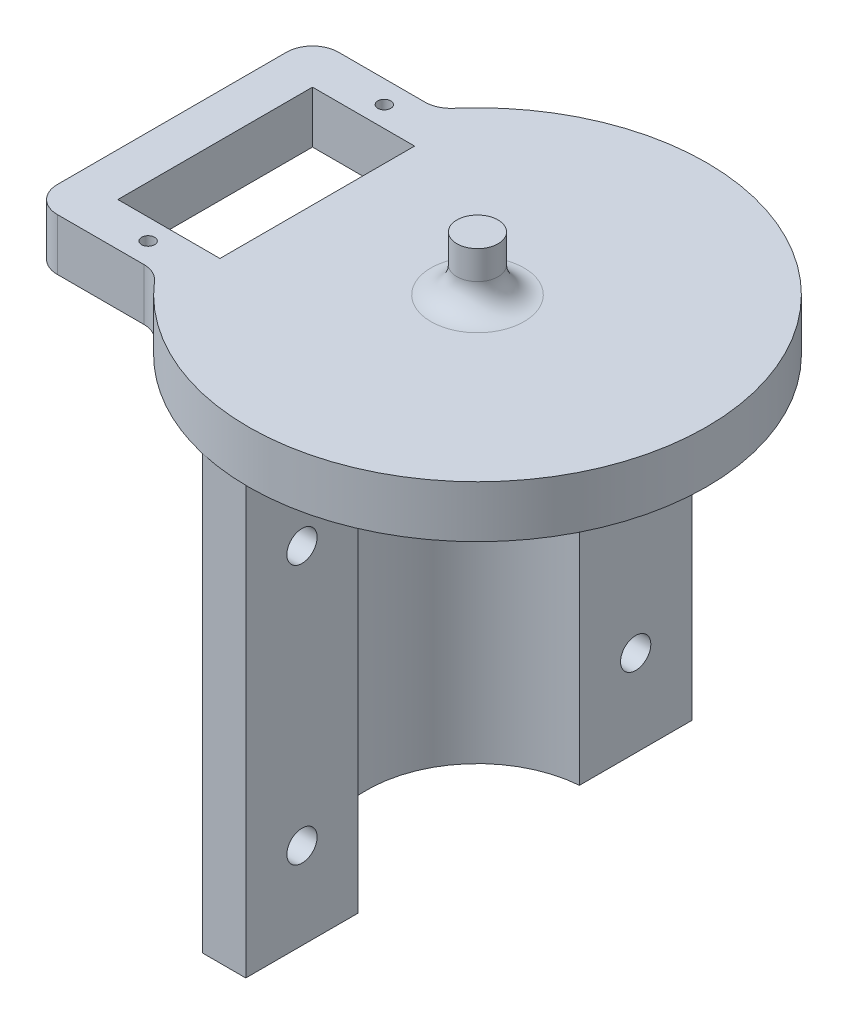
SolidWorks part; units mm, degrees
ref_plane "Front Plane" through (0, 0, 0) normal (0, 0, 1) x (1, 0, 0)
ref_plane "Top Plane" through (0, 0, 0) normal (0, 1, 0) x (1, 0, 0)
ref_plane "Right Plane" through (0, 0, 0) normal (1, 0, 0) x (0, 0, -1)
sketch "Sketch6" plane through (0, 0, 0) normal (0, -1, 0) x (1, 0, 0)
  line L5 (-1, 25.7848) -> (-1, 12.786)
  line L6 (-1, 25.7848) -> (-6, 25.7848)
  line L7 (-6, 25.7848) -> (-6, 16.7848)
  line L8 (-6, -16.7848) -> (-6, -25.7848)
  line L9 (-6, -25.7848) -> (-1, -25.7848)
  line L10 (-1, -25.7848) -> (-1, -12.786)
  line L11 (-12.825, 0) -> (-17.825, 0) construction
  arc A0 (-1, 12.786) -> (-1, -12.786) centre (0, 0) ccw
  arc A1 (-6, 16.7848) -> (-6, -16.7848) centre (0, 0) ccw
  dimension "D1" = 25.65
  dimension "D2" = 5
  dimension "D3" = 1
  dimension "D4" = 9
extrude "Boss-Extrude4" add sketch "Sketch6" along normal blind 50
sketch "Sketch7" plane through (-1, 0, 0) normal (1, 0, 0) x (0, 0, -1)
  line L0 (-19.2854, -50) -> (-19.2854, 0) construction
  line L3 (0, 0) -> (0, -50) construction
  line L6 (-25.7848, -25) -> (25.7848, -25) construction
  line L11 (-12.786, 0) -> (-25.7848, 0) construction
  line L12 (-12.786, -50) -> (-25.7848, -50) construction
  line L13 (-25.7848, -50) -> (-25.7848, 0) construction
  line L14 (25.7848, -50) -> (25.7848, 0) construction
  line L15 (-12.786, -50) -> (12.786, -50) construction
  circle A0 centre (-19.2854, -10) radius 1.75
  circle A1 centre (-19.2854, -40) radius 1.75
  circle A2 centre (19.2854, -40) radius 1.75
  circle A3 centre (19.2854, -10) radius 1.75
  dimension "D1" = 10
  dimension "D2" = 3.5
extrude "Cut-Extrude1" cut sketch "Sketch7" against normal through all
sketch "Sketch8" plane through (0, 0, 0) normal (0, 1, 0) x (1, 0, 0)
  line L0 (-24.4208, -13.65) -> (-24.4208, 13.65) construction
  line L1 (-30.3208, -11.25) -> (-18.5208, -11.25)
  line L2 (-30.3208, -11.25) -> (-30.3208, 11.25)
  line L3 (-30.3208, 11.25) -> (-18.5208, 11.25)
  line L4 (-18.5208, -11.25) -> (-18.5208, 11.25)
  line L5 (-32.3208, -16.25) -> (-22.319, -16.25)
  line L6 (-35.3208, -13.25) -> (-35.3208, 13.25)
  line L7 (-32.3208, 16.25) -> (-22.319, 16.25)
  circle A1 centre (-24.4208, 13.65) radius 0.75
  circle A2 centre (-24.4208, -13.65) radius 0.75
  arc A3 (-20.0472, -17.2906) -> (-20.0472, 17.2906) centre (0, 0) ccw
  arc A4 (-32.3208, -16.25) -> (-35.3208, -13.25) centre (-32.3208, -13.25) cw
  arc A5 (-35.3208, 13.25) -> (-32.3208, 16.25) centre (-32.3208, 13.25) cw
  arc A6 (-22.319, 16.25) -> (-20.0472, 17.2906) centre (-22.319, 19.25) ccw
  arc A7 (-22.319, -16.25) -> (-20.0472, -17.2906) centre (-22.319, -19.25) cw
  circle A8 centre (-24.4208, 5.35) radius 5.9 construction
  point P7 (-18.5208, 0)
  point P13 (-24.4208, -11.25)
  point P18 (-24.4208, 0)
  point P24 (-35.3208, 0)
  dimension "D1" = 5
  dimension "D4" = 1.5
  dimension "D7" = 5
  dimension "D8" = 3
  dimension "D9" = 3
  dimension "D10" = 11.8
  dimension "D2" = 11.8
  dimension "D3" = 22.5
  dimension "D5" = 27.3
  dimension "D6" = 25
extrude "Boss-Extrude5" add sketch "Sketch8" along normal blind 6
sketch "Sketch9" plane through (0, 6, 0) normal (0, 1, 0) x (1, 0, 0)
  circle A0 centre (0, 0) radius 2.3813
  dimension "D1" = 4.7625
extrude "Boss-Extrude6" add sketch "Sketch9" along normal blind 6.3
fillet "Fillet1" radius 3 1 edges at (0, 6, 2.3813)
